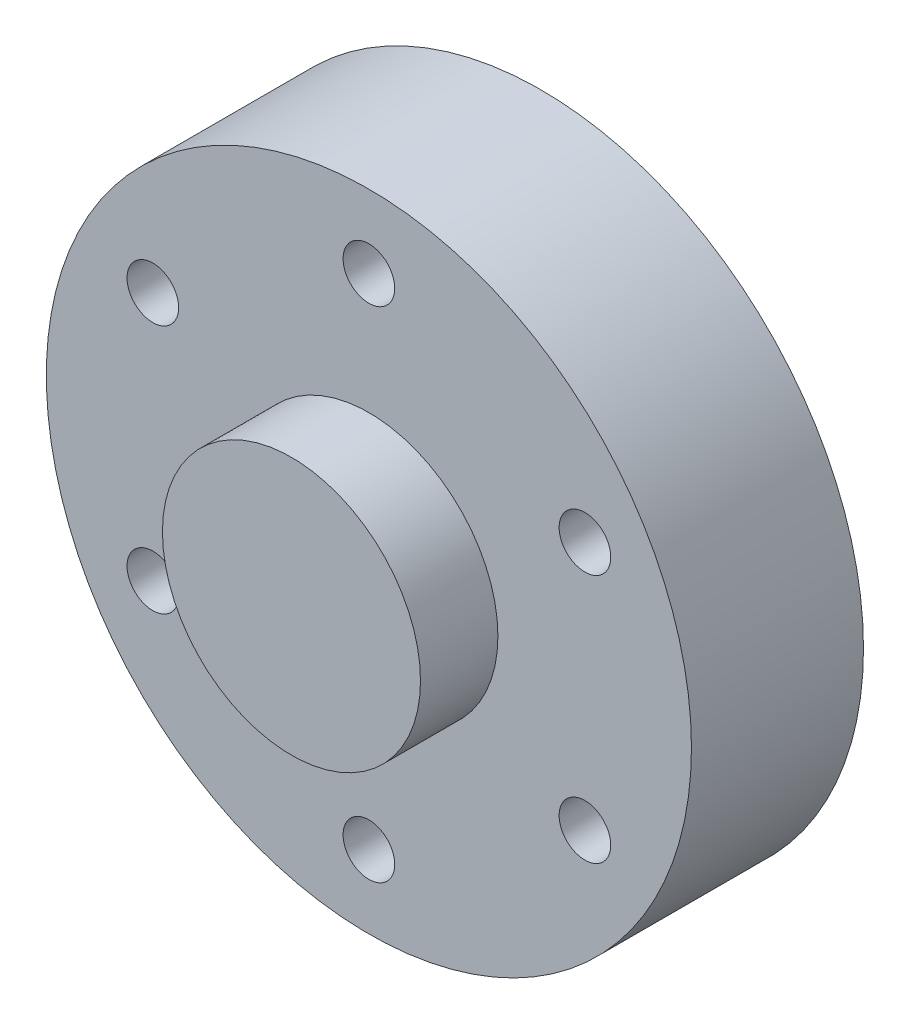
SolidWorks part; units mm, degrees
ref_plane "Front Plane" through (0, 0, 0) normal (0, 0, 1) x (1, 0, 0)
ref_plane "Top Plane" through (0, 0, 0) normal (0, 1, 0) x (1, 0, 0)
ref_plane "Right Plane" through (0, 0, 0) normal (1, 0, 0) x (0, 0, -1)
sketch "Sketch2" plane through (0, 0, 0) normal (0, 0, 1) x (1, 0, 0)
  circle A0 centre (0, 0) radius 9.5
  circle A1 centre (0, 0) radius 14.5 construction
  circle A3 centre (0, 0) radius 18.75
  circle A4 centre (0, 14.5) radius 1.5
  circle A5 centre (12.5574, 7.25) radius 1.5
  circle A6 centre (12.5574, -7.25) radius 1.5
  circle A7 centre (0, -14.5) radius 1.5
  circle A8 centre (-12.5574, -7.25) radius 1.5
  circle A9 centre (-12.5574, 7.25) radius 1.5
  point P21 (0, 0)
  dimension "D1" = 19
  dimension "D3" = 29
  dimension "D4" = 37.5
  dimension "D5" = 3
  dimension "D6" = 6
extrude "Boss-Extrude1" add sketch "Sketch2" along normal blind 10 contours A3 A9 A8 A7 A6 A5 A4 A0 | A0 region at (0, 0, 0) region at (-18.2197, 0, 0)
sketch "Sketch3" plane through (0, 0, 10) normal (0, 0, 1) x (1, 0, 0)
  circle A0 centre (0, 0) radius 7.5
  dimension "D1" = 15
extrude "Boss-Extrude2" add sketch "Sketch3" along normal blind 4.5
sketch "Sketch6" plane through (0, 0, 0) normal (0, 0, -1) x (-1, 0, 0)
  circle A0 centre (0, 0) radius 7.5
  dimension "D1" = 15
extrude "Boss-Extrude4" add sketch "Sketch6" along normal blind 4.5 contours A0
sketch "Sketch7" plane through (0, 0, -4.5) normal (0, 0, -1) x (-1, 0, 0)
  circle A0 centre (0, 0) radius 2
  dimension "D1" = 4
extrude "Boss-Extrude5" add sketch "Sketch7" along normal blind 1
fillet "Fillet2" radius 0.05 1 edges at (-2, 0, -5.5)
sketch "Sketch9" plane through (0, 0, -5.5) normal (0, 0, -1) x (-1, 0, 0)
  line L1 (-1.2042, 1.2) -> (1.2042, 1.2)
  arc A0 (-1.2042, 1.2) -> (1.2042, 1.2) centre (0, 0) ccw
  circle A1 centre (0, -0.25) radius 1.45 construction
  point P3 (0, -0.181)
  dimension "D1" = 3.4
  dimension "D2" = 2.9
extrude "Cut-Extrude1" cut sketch "Sketch9" against normal blind 11
